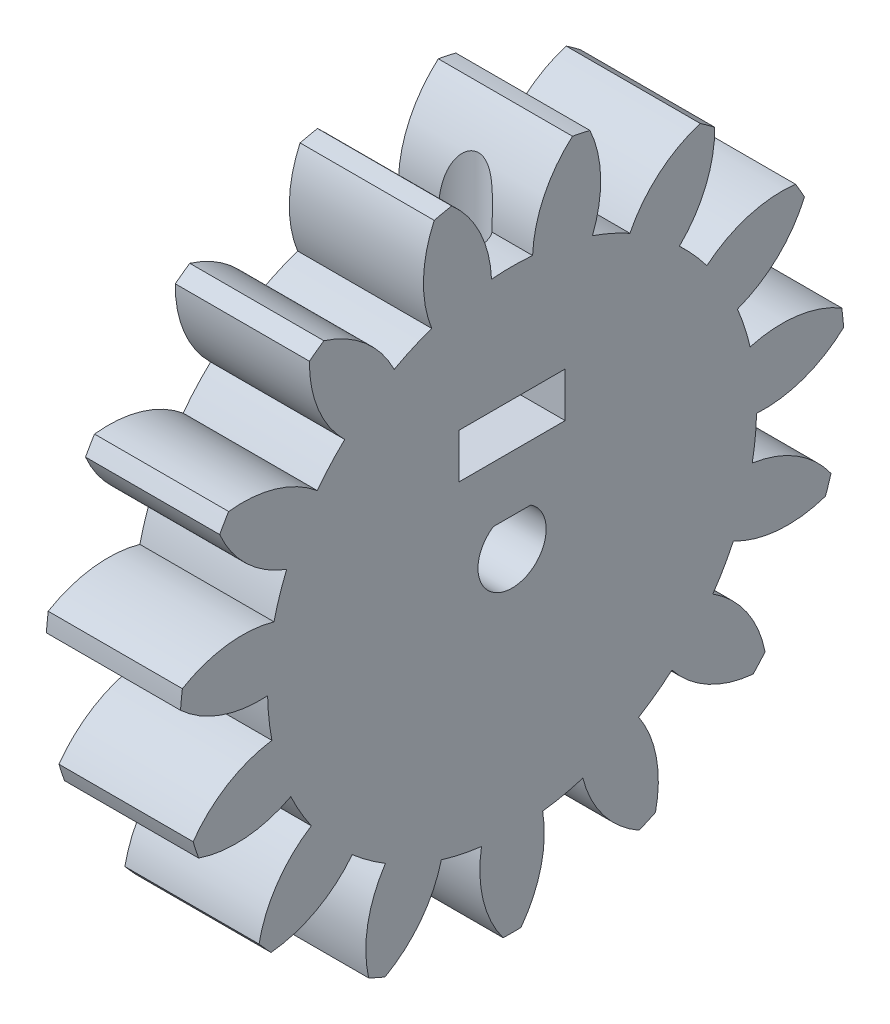
SolidWorks part; units mm, degrees
other "Markup1"
sketch "Sketch16" plane through (0, 29.2556, 29.6599) normal (0, 1, 0) x (0, 0, -1)
ref_plane "Plane1" through (0, 0, 0) normal (0, 0, 1) x (1, 0, 0)
ref_plane "Plane2" through (0, 0, 0) normal (0, 1, 0) x (1, 0, 0)
ref_plane "Plane3" through (0, 0, 0) normal (1, 0, 0) x (0, 0, -1)
sketch "HoldingSke" plane through (0, 0, 0) normal (0, 1, 0) x (1, 0, 0)
  line L0 (0, 0) -> (0.276, -0.0739)
  line L1 (-15, 0) -> (100, 0) construction
  line L2 (0, 0) -> (-2.1039, 2.3779)
  line L3 (0, 0) -> (-11.863, 4.5341)
  line L4 (0, 0) -> (8.3417, 2.2352)
  line L5 (0, 0) -> (-46.8476, -17.4728)
  line L6 (0, 0) -> (-8.2896, -5.593)
  line L7 (-2.1039, 2.3779) -> (8.6586, 51.2059)
  line L8 (-76.2, 54.61) -> (-75.2, 54.61)
  line L9 (-71.009, 38.7566) -> (-53.1078, 45.2721)
  line L10 (-76.2, 71.12) -> (104.1128, 71.12)
  line L11 (0, 0) -> (-10, 0)
  line L12 (-76.2, 101.6) -> (-76.083, 101.6)
  line L13 (24.9733, 27.94) -> (52.9518, 28.4284)
  line L14 (24.9733, 27.94) -> (24.9743, 27.94)
  line L15 (24.9733, 27.94) -> (100.4006, 29.5858)
  line L16 (-63.627, -3.5) -> (-12.827, -3.5)
  circle A0 centre (0, 0) radius 3
  circle A1 centre (0, 0) radius 21.874
  circle A2 centre (0, 0) radius 37.5
  circle A3 centre (0, 0) radius 3
  dimension "MHD" = 43.748
  dimension "Hub_dia" = 75
  dimension "Bore" = 6
  dimension "MBD" = 6
  dimension "Num_teeth" = 15
  dimension "Pitch" = 0.2857
  dimension "Overall_len" = 50
  dimension "Show_teeth" = 15
  dimension "Thickness" = 10
  dimension "OAL" = 50.0001
  dimension "T_dim" = 1
  dimension "Ap" = 20
  dimension "H" = 19.05
  dimension "Pitch_radius" = 180.3128
  dimension "Width" = 10
  dimension "Backlash" = 0.117
  dimension "Addendum_fac" = 1
  dimension "Dedendum_fac" = 1.25
  dimension "Clearance_fac" = 0.25
  dimension "Dedendum_add" = 0.001
  dimension "Module" = 3.5
sketch "BasProSke" plane through (0, 0, 0) normal (0, 1, 0) x (1, 0, 0)
  line L0 (-10, 0) -> (60, 0) construction
  line L1 (0, 0) -> (0, 29.75)
  line L2 (0, 0) -> (10, 0)
  line L3 (10, 0) -> (10, 29.75)
  line L4 (10, 29.75) -> (0, 29.75)
  dimension "Thickness" = 10
  dimension "Diameter" = 59.5
revolve "Base-Revolve" add sketch "BasProSke" angle 360 about L0
sketch "TooCutSke" plane through (0, 0, 0) normal (1, 0, 0) x (0, 0, -1)
  line L1 (0, 0) -> (0, 107) construction
  line L2 (0, 0) -> (-2.9485, 26.0839) construction
  line L3 (0, 0) -> (-10.8642, 51.1119) construction
  line L4 (-2.9485, 26.0839) -> (-5.4321, 25.556) construction
  arc A0 (1.8373, 21.7967) -> (-1.8373, 21.7967) centre (0, 0) ccw
  arc A1 (5.4253, 29.277) -> (-5.4253, 29.277) centre (0, 0) ccw
  circle A2 centre (0, 0) radius 26.25 construction
  circle A3 centre (0, 0) radius 24.6669 construction
  arc A4 (-1.8373, 21.7967) -> (-5.4253, 29.277) centre (-12.3284, 21.3651) ccw
  arc A5 (5.4253, 29.277) -> (1.8373, 21.7967) centre (12.3284, 21.3651) ccw
  dimension "Root_dia" = 43.748
  dimension "Overcut_dia" = 59.5508
  dimension "Pitch_dia" = 52.5
  dimension "Base_dia" = 49.3339
  dimension "Flank_rad" = 10.5
  dimension "Half_ang" = 12
  dimension "Half_CT" = 2.5391
extrude "ToothCut" cut sketch "TooCutSke" along normal through all
fillet "Breaks" [suppressed] radius 0.07 tangent propagation no
fillet "RootFillets" [suppressed] radius 0.876
pattern_circular "TeethCuts" count 15 every 24 about axis through (-10, 0, 0) along (1, 0, 0) of "ToothCut", "RootFillets", "Breaks"
sketch "HubNeaOneSke" plane through (0, 0, 0) normal (-1, 0, 0) x (0, 0, 1)
  circle A0 centre (0, 0) radius 21.874
  dimension "Diameter" = 43.748
extrude "HubNearOne" [suppressed] add sketch "HubNeaOneSke" along normal blind 40.0001
sketch "HubNeaBotSke" plane through (0, 0, 0) normal (-1, 0, 0) x (0, 0, 1)
  circle A0 centre (0, 0) radius 21.874
  dimension "Diameter" = 43.748
extrude "HubNearBoth" [suppressed] add sketch "HubNeaBotSke" along normal blind 20
ref_plane "FarPln" through (10, 0, 0) normal (1, 0, 0) x (0, 0, -1)
sketch "HubFarSke" plane through (10, 0, 0) normal (1, 0, 0) x (0, 0, -1)
  circle A0 centre (0, 0) radius 21.874
  dimension "Diameter" = 43.748
extrude "HubFar" [suppressed] add sketch "HubFarSke" along normal blind 20
sketch "BorSke" plane through (0, 0, 0) normal (1, 0, 0) x (0, 0, -1)
  circle A0 centre (0, 0) radius 3
  dimension "Diameter" = 6
extrude "Bore" cut sketch "BorSke" along normal mid plane 100.0001
sketch "KeySke" plane through (0, 0, 0) normal (1, 0, 0) x (0, 0, -1)
  line L0 (-1, 0) -> (-1, 4)
  line L1 (-1, 4) -> (1, 4)
  line L2 (1, 4) -> (1, 0)
  line L3 (0, 0) -> (0, 34) construction
  line L4 (-1, 0) -> (1, 0)
  dimension "Offset" = 4
  dimension "Width" = 2
extrude "Keyway" [suppressed] cut sketch "KeySke" along normal mid plane 100.0001
pattern_circular "Keyway2" [suppressed] count 2 every 90 about axis through (-10, 0, 0) along (1, 0, 0) reverse direction yes
sketch "Sketch1" plane through (0, 0, 0) normal (-1, 0, 0) x (0, 0, 1)
  circle A0 centre (0, 0) radius 3.05
  dimension "D1" = 6.1
extrude "Cut-Extrude1" cut sketch "Sketch1" against normal blind 10
sketch "Sketch2" plane through (0, 0, 0) normal (-1, 0, 0) x (0, 0, 1)
  circle A0 centre (0, 0) radius 4.0254
extrude "Boss-Extrude1" add sketch "Sketch2" against normal blind 4
sketch "Sketch5" plane through (10, 0, 0) normal (1, 0, 0) x (0, 0, -1)
  line L5 (5.1432, 3.05) -> (-4.9527, 3.05)
  line L6 (5.1432, 3.05) -> (5.1432, 2.55)
  line L7 (5.1432, 2.55) -> (-4.9527, 2.55)
  line L8 (-4.9527, 3.05) -> (-4.9527, 2.55)
  dimension "D1" = 0.5
extrude "Boss-Extrude5" add sketch "Sketch5" against normal blind 6
sketch "Sketch6" plane through (0, 0, 0) normal (-1, 0, 0) x (0, 0, 1)
  line L5 (-0.625, -1.625) -> (0.625, -1.625)
  line L6 (-0.625, -1.625) -> (-0.625, 1.625)
  line L7 (-0.625, 1.625) -> (0.625, 1.625)
  line L8 (0.625, -1.625) -> (0.625, 1.625)
  dimension "D2" = 1.25
  dimension "D3" = 3.25
extrude "Cut-Extrude2" cut sketch "Sketch6" against normal blind 3.25
sketch "Sketch7" plane through (0, 0, 0) normal (0, 1, 0) x (1, 0, 0)
  line L0 (10, -1.8373) -> (10, 1.8373) construction
  circle A0 centre (6, 0) radius 1.5
  dimension "D1" = 3
  dimension "D2" = 4
extrude "Cut-Extrude3" cut sketch "Sketch7" against normal blind 30 from offset 30
sketch "Sketch8" plane through (0, 0, 0) normal (0, 1, 0) x (1, 0, 0)
  circle A0 centre (6, 0) radius 3
  dimension "D1" = 6
extrude "Cut-Extrude4" cut sketch "Sketch8" against normal blind 14 from offset 30
sketch "Sketch11" plane through (10, 0, 0) normal (1, 0, 0) x (0, 0, -1)
  arc A60 (-29.6599, 2.3133) -> (-21.8693, -0.4512) centre (-22.5367, 10.0276) ccw
  arc A61 (-21.8693, -0.4512) -> (-21.4853, -4.1056) centre (0, 0) ccw
  arc A62 (-21.4853, -4.1056) -> (-28.5308, -8.4294) centre (-19.9594, -14.4941) ccw
  arc A63 (-28.5308, -8.4294) -> (-28.0366, -9.9505) centre (0, 0) ccw
  arc A64 (-28.0366, -9.9505) -> (-19.7951, -9.3072) centre (-24.6669, -0.0059) ccw
  arc A65 (-19.7951, -9.3072) -> (-17.9579, -12.4895) centre (0, 0) ccw
  arc A66 (-17.9579, -12.4895) -> (-22.6357, -19.3052) centre (-12.3385, -21.3593) ccw
  arc A67 (-22.6357, -19.3052) -> (-21.5655, -20.4937) centre (0, 0) ccw
  arc A68 (-21.5655, -20.4937) -> (-14.2982, -16.554) centre (-22.532, -10.0383) ccw
  arc A69 (-14.2982, -16.554) -> (-11.3254, -18.7138) centre (0, 0) ccw
  arc A70 (-11.3254, -18.7138) -> (-12.8266, -26.8429) centre (-2.5842, -24.5312) ccw
  arc A71 (-12.8266, -26.8429) -> (-11.3655, -27.4934) centre (0, 0) ccw
  arc A72 (-11.3655, -27.4934) -> (-6.3289, -20.9384) centre (-16.501, -18.335) ccw
  arc A73 (-6.3289, -20.9384) -> (-2.7347, -21.7024) centre (0, 0) ccw
  arc A74 (-2.7347, -21.7024) -> (-0.7997, -29.7393) centre (7.6169, -23.4615) ccw
  arc A75 (-0.7997, -29.7393) -> (0.7997, -29.7393) centre (0, 0) ccw
  arc A76 (0.7997, -29.7393) -> (2.7347, -21.7024) centre (-7.6169, -23.4615) ccw
  arc A77 (2.7347, -21.7024) -> (6.3289, -20.9384) centre (0, 0) ccw
  arc A78 (6.3289, -20.9384) -> (11.3655, -27.4934) centre (16.501, -18.335) ccw
  arc A79 (11.3655, -27.4934) -> (12.8266, -26.8429) centre (0, 0) ccw
  arc A80 (12.8266, -26.8429) -> (11.3254, -18.7138) centre (2.5842, -24.5312) ccw
  arc A81 (11.3254, -18.7138) -> (14.2982, -16.554) centre (0, 0) ccw
  arc A82 (14.2982, -16.554) -> (21.5655, -20.4937) centre (22.532, -10.0383) ccw
  arc A83 (21.5655, -20.4937) -> (22.6357, -19.3052) centre (0, 0) ccw
  arc A84 (22.6357, -19.3052) -> (17.9579, -12.4895) centre (12.3385, -21.3593) ccw
  arc A85 (17.9579, -12.4895) -> (19.7951, -9.3072) centre (0, 0) ccw
  arc A86 (19.7951, -9.3072) -> (28.0366, -9.9505) centre (24.6669, -0.0059) ccw
  arc A87 (28.0366, -9.9505) -> (28.5308, -8.4294) centre (0, 0) ccw
  arc A88 (28.5308, -8.4294) -> (21.4853, -4.1056) centre (19.9594, -14.4941) ccw
  arc A89 (21.4853, -4.1056) -> (21.8693, -0.4512) centre (0, 0) ccw
  arc A90 (21.8693, -0.4512) -> (29.6599, 2.3133) centre (22.5367, 10.0276) ccw
  arc A91 (29.6599, 2.3133) -> (29.4927, 3.9039) centre (0, 0) ccw
  arc A92 (29.4927, 3.9039) -> (21.2976, 4.9882) centre (24.1291, -5.1228) ccw
  arc A93 (21.2976, 4.9882) -> (20.1622, 8.4829) centre (0, 0) ccw
  arc A94 (20.1622, 8.4829) -> (26.1548, 14.1771) centre (16.5098, 18.3272) ccw
  arc A95 (26.1548, 14.1771) -> (25.3551, 15.5622) centre (0, 0) ccw
  arc A96 (25.3551, 15.5622) -> (17.4275, 13.2195) centre (24.1267, 5.1343) ccw
  arc A97 (17.4275, 13.2195) -> (14.9687, 15.9502) centre (0, 0) ccw
  arc A98 (14.9687, 15.9502) -> (18.1272, 23.5895) centre (7.6281, 23.4578) ccw
  arc A99 (18.1272, 23.5895) -> (16.8333, 24.5296) centre (0, 0) ccw
  arc A100 (16.8333, 24.5296) -> (10.5439, 19.165) centre (19.9525, 14.5036) ccw
  arc A101 (10.5439, 19.165) -> (7.1871, 20.6596) centre (0, 0) ccw
  arc A102 (7.1871, 20.6596) -> (6.9653, 28.9231) centre (-2.5726, 24.5324) ccw
  arc A103 (6.9653, 28.9231) -> (5.4009, 29.2556) centre (0, 0) ccw
  arc A104 (5.4009, 29.2556) -> (1.8373, 21.7967) centre (12.3284, 21.3651) ccw
  arc A105 (1.8373, 21.7967) -> (-1.8373, 21.7967) centre (0, 0) ccw
  arc A106 (-1.8373, 21.7967) -> (-5.4009, 29.2556) centre (-12.3284, 21.3651) ccw
  arc A107 (-5.4009, 29.2556) -> (-6.9653, 28.9231) centre (0, 0) ccw
  arc A108 (-6.9653, 28.9231) -> (-7.1871, 20.6596) centre (2.5726, 24.5324) ccw
  arc A109 (-7.1871, 20.6596) -> (-10.5439, 19.165) centre (0, 0) ccw
  arc A110 (-10.5439, 19.165) -> (-16.8333, 24.5296) centre (-19.9525, 14.5036) ccw
  arc A111 (-16.8333, 24.5296) -> (-18.1272, 23.5895) centre (0, 0) ccw
  arc A112 (-18.1272, 23.5895) -> (-14.9687, 15.9502) centre (-7.6281, 23.4578) ccw
  arc A113 (-14.9687, 15.9502) -> (-17.4275, 13.2195) centre (0, 0) ccw
  arc A114 (-17.4275, 13.2195) -> (-25.3551, 15.5622) centre (-24.1267, 5.1343) ccw
  arc A115 (-25.3551, 15.5622) -> (-26.1548, 14.1771) centre (0, 0) ccw
  arc A116 (-26.1548, 14.1771) -> (-20.1622, 8.4829) centre (-16.5098, 18.3272) ccw
  arc A117 (-20.1622, 8.4829) -> (-21.2976, 4.9882) centre (0, 0) ccw
  arc A118 (-21.2976, 4.9882) -> (-29.4927, 3.9039) centre (-24.1291, -5.1228) ccw
  arc A119 (-29.4927, 3.9039) -> (-29.6599, 2.3133) centre (0, 0) ccw
  arc A120 (-29.6599, 2.3133) -> (-21.8693, -0.4512) centre (-22.5367, 10.0276) ccw
  arc A121 (-21.8693, -0.4512) -> (-21.4853, -4.1056) centre (0, 0) ccw
  arc A122 (-21.4853, -4.1056) -> (-28.5308, -8.4294) centre (-19.9594, -14.4941) ccw
  arc A123 (-28.5308, -8.4294) -> (-28.0366, -9.9505) centre (0, 0) ccw
  arc A124 (-28.0366, -9.9505) -> (-19.7951, -9.3072) centre (-24.6669, -0.0059) ccw
  arc A125 (-19.7951, -9.3072) -> (-17.9579, -12.4895) centre (0, 0) ccw
  arc A126 (-17.9579, -12.4895) -> (-22.6357, -19.3052) centre (-12.3385, -21.3593) ccw
  arc A127 (-22.6357, -19.3052) -> (-21.5655, -20.4937) centre (0, 0) ccw
  arc A128 (-21.5655, -20.4937) -> (-14.2982, -16.554) centre (-22.532, -10.0383) ccw
  arc A129 (-14.2982, -16.554) -> (-11.3254, -18.7138) centre (0, 0) ccw
  arc A130 (-11.3254, -18.7138) -> (-12.8266, -26.8429) centre (-2.5842, -24.5312) ccw
  arc A131 (-12.8266, -26.8429) -> (-11.3655, -27.4934) centre (0, 0) ccw
  arc A132 (-11.3655, -27.4934) -> (-6.3289, -20.9384) centre (-16.501, -18.335) ccw
  arc A133 (-6.3289, -20.9384) -> (-2.7347, -21.7024) centre (0, 0) ccw
  arc A134 (-2.7347, -21.7024) -> (-0.7997, -29.7393) centre (7.6169, -23.4615) ccw
  arc A135 (-0.7997, -29.7393) -> (0.7997, -29.7393) centre (0, 0) ccw
  arc A136 (0.7997, -29.7393) -> (2.7347, -21.7024) centre (-7.6169, -23.4615) ccw
  arc A137 (2.7347, -21.7024) -> (6.3289, -20.9384) centre (0, 0) ccw
  arc A138 (6.3289, -20.9384) -> (11.3655, -27.4934) centre (16.501, -18.335) ccw
  arc A139 (11.3655, -27.4934) -> (12.8266, -26.8429) centre (0, 0) ccw
  arc A140 (12.8266, -26.8429) -> (11.3254, -18.7138) centre (2.5842, -24.5312) ccw
  arc A141 (11.3254, -18.7138) -> (14.2982, -16.554) centre (0, 0) ccw
  arc A142 (14.2982, -16.554) -> (21.5655, -20.4937) centre (22.532, -10.0383) ccw
  arc A143 (21.5655, -20.4937) -> (22.6357, -19.3052) centre (0, 0) ccw
  arc A144 (22.6357, -19.3052) -> (17.9579, -12.4895) centre (12.3385, -21.3593) ccw
  arc A145 (17.9579, -12.4895) -> (19.7951, -9.3072) centre (0, 0) ccw
  arc A146 (19.7951, -9.3072) -> (28.0366, -9.9505) centre (24.6669, -0.0059) ccw
  arc A147 (28.0366, -9.9505) -> (28.5308, -8.4294) centre (0, 0) ccw
  arc A148 (28.5308, -8.4294) -> (21.4853, -4.1056) centre (19.9594, -14.4941) ccw
  arc A149 (21.4853, -4.1056) -> (21.8693, -0.4512) centre (0, 0) ccw
  arc A150 (21.8693, -0.4512) -> (29.6599, 2.3133) centre (22.5367, 10.0276) ccw
  arc A151 (29.6599, 2.3133) -> (29.4927, 3.9039) centre (0, 0) ccw
  arc A152 (29.4927, 3.9039) -> (21.2976, 4.9882) centre (24.1291, -5.1228) ccw
  arc A153 (21.2976, 4.9882) -> (20.1622, 8.4829) centre (0, 0) ccw
  arc A154 (20.1622, 8.4829) -> (26.1548, 14.1771) centre (16.5098, 18.3272) ccw
  arc A155 (26.1548, 14.1771) -> (25.3551, 15.5622) centre (0, 0) ccw
  arc A156 (25.3551, 15.5622) -> (17.4275, 13.2195) centre (24.1267, 5.1343) ccw
  arc A157 (17.4275, 13.2195) -> (14.9687, 15.9502) centre (0, 0) ccw
  arc A158 (14.9687, 15.9502) -> (18.1272, 23.5895) centre (7.6281, 23.4578) ccw
  arc A159 (18.1272, 23.5895) -> (16.8333, 24.5296) centre (0, 0) ccw
  arc A160 (16.8333, 24.5296) -> (10.5439, 19.165) centre (19.9525, 14.5036) ccw
  arc A161 (10.5439, 19.165) -> (7.1871, 20.6596) centre (0, 0) ccw
  arc A162 (7.1871, 20.6596) -> (6.9653, 28.9231) centre (-2.5726, 24.5324) ccw
  arc A163 (6.9653, 28.9231) -> (5.4009, 29.2556) centre (0, 0) ccw
  arc A164 (5.4009, 29.2556) -> (1.8373, 21.7967) centre (12.3284, 21.3651) ccw
  arc A165 (1.8373, 21.7967) -> (-1.8373, 21.7967) centre (0, 0) ccw
  arc A166 (-1.8373, 21.7967) -> (-5.4009, 29.2556) centre (-12.3284, 21.3651) ccw
  arc A167 (-5.4009, 29.2556) -> (-6.9653, 28.9231) centre (0, 0) ccw
  arc A168 (-6.9653, 28.9231) -> (-7.1871, 20.6596) centre (2.5726, 24.5324) ccw
  arc A169 (-7.1871, 20.6596) -> (-10.5439, 19.165) centre (0, 0) ccw
  arc A170 (-10.5439, 19.165) -> (-16.8333, 24.5296) centre (-19.9525, 14.5036) ccw
  arc A171 (-16.8333, 24.5296) -> (-18.1272, 23.5895) centre (0, 0) ccw
  arc A172 (-18.1272, 23.5895) -> (-14.9687, 15.9502) centre (-7.6281, 23.4578) ccw
  arc A173 (-14.9687, 15.9502) -> (-17.4275, 13.2195) centre (0, 0) ccw
  arc A174 (-17.4275, 13.2195) -> (-25.3551, 15.5622) centre (-24.1267, 5.1343) ccw
  arc A175 (-25.3551, 15.5622) -> (-26.1548, 14.1771) centre (0, 0) ccw
  arc A176 (-26.1548, 14.1771) -> (-20.1622, 8.4829) centre (-16.5098, 18.3272) ccw
  arc A177 (-20.1622, 8.4829) -> (-21.2976, 4.9882) centre (0, 0) ccw
  arc A178 (-21.2976, 4.9882) -> (-29.4927, 3.9039) centre (-24.1291, -5.1228) ccw
  arc A179 (-29.4927, 3.9039) -> (-29.6599, 2.3133) centre (0, 0) ccw
  dimension "D1" = 0
extrude "Boss-Extrude7" add sketch "Sketch11" along normal blind 2
sketch "Sketch12" plane through (12, 0, 0) normal (1, 0, 0) x (0, 0, -1)
  circle A0 centre (0, 0) radius 3.05
  dimension "D1" = 6.1
extrude "Cut-Extrude5" cut sketch "Sketch12" against normal blind 2
extrude "Boss-Extrude8" add sketch "Sketch5<2>" along normal blind 2
sketch "Sketch5<2>" plane through (10, 0, 0) normal (1, 0, 0) x (0, 0, -1) same geometry as "Sketch5"
sketch "Sketch15" plane through (0, 16, 0) normal (0, 1, 0) x (1, 0, 0)
  circle A0 centre (6, 0) radius 1.75
  dimension "D1" = 3.5
extrude "Cut-Extrude6" cut sketch "Sketch15" against normal blind 16
sketch "Sketch18" plane through (12, 0, 0) normal (1, 0, 0) x (0, 0, -1)
  line L0 (1.6733, 2.55) -> (-1.6733, 2.55) construction
  line L1 (-4.75, 7.55) -> (4.75, 7.55)
  line L2 (-4.75, 7.55) -> (-4.75, 11.55)
  line L3 (-4.75, 11.55) -> (4.75, 11.55)
  line L4 (4.75, 7.55) -> (4.75, 11.55)
  line L5 (-4.75, 7.55) -> (4.75, 11.55) construction
  line L6 (-4.75, 11.55) -> (4.75, 7.55) construction
  line L7 (0, 2.55) -> (0, 7.55)
  point P0 (0, 9.55)
  dimension "D1" = 4
  dimension "D2" = 9.5
  dimension "D3" = 5
  dimension "D4" = 90
extrude "Cut-Extrude7" cut sketch "Sketch18" against normal through all contours L1 L4 L3 L2 region at (12, 9.55, 0)
sketch "Sketch20" plane through (0, 16, 0) normal (0, 1, 0) x (1, 0, 0)
  circle A1 centre (6, 0) radius 3
  circle A2 centre (6, 0) radius 3
  dimension "D1" = 0
extrude "Cut-Extrude9" cut sketch "Sketch20" against normal up to surface (4.45 mm away) contours A2 up to face at (6, 11.55, 0)
equation "' \"Module@HoldingSke\" = 6.35"
equation "' \"Num_teeth@HoldingSke\" = 12"
equation "' \"Ap@HoldingSke\" =  20"
equation "' \"Ap@HoldingSke\" = 20"
equation "' \"Width@HoldingSke\" = 0.5 * 25.4"
equation "' \"Hub_dia@HoldingSke\"= 1 * 25.4"
equation "' \"Hub_dia@HoldingSke\" = 1 * 25.4"
equation "' \"Overall_len@HoldingSke\" = 1.0 * 25.4"
equation "' \"Bore@HoldingSke\" = 0.75 * 25.4"
equation "' \"T_dim@HoldingSke\" = 0.1 * 25.4"
equation "' \"Width@KeySke\" = 0.25 * 25.4"
equation "' \"Show_teeth@HoldingSke\" = 13"
equation "' \"Backlash@HoldingSke\" = 0.009 * 25.4"
equation "' \"Addendum_fac@HoldingSke\" = 1.0"
equation "' \"Dedendum_fac@HoldingSke\" = 1.25"
equation "' \"Dedendum_add@HoldingSke\" = 0.00005 * 25.4"
equation "' \"Clearance_fac@HoldingSke\" = 0.25"
equation "\"Pitch@HoldingSke\" = 1 / \"Module@HoldingSke\""
equation "\"Overcut_dia@TooCutSke\" = (\"Num_teeth@HoldingSke\" + 2 * \"Addendum_fac@HoldingSke\") / \"Pitch@HoldingSke\" + 0.002 * 25.4"
equation "\"Pitch_dia@TooCutSke\" = \"Num_teeth@HoldingSke\" / \"Pitch@HoldingSke\""
equation "\"Base_dia@TooCutSke\" = \"Num_teeth@HoldingSke\" / \"Pitch@HoldingSke\" * cos((\"Ap@HoldingSke\"  * 3.14159265 / 180))"
equation "\"Root_dia@TooCutSke\" = (\"Num_teeth@HoldingSke\" + 2) / \"Pitch@HoldingSke\" - 2 * (\"Addendum_fac@HoldingSke\" + \"Dedendum_fac@HoldingSke\") / \"Pitch@HoldingSke\" - \"Dedendum_add@HoldingSke\" * 2"
equation "\"Half_ang@TooCutSke\" = 180 / \"Num_teeth@HoldingSke\""
equation "\"Half_CT@TooCutSke\" = \"Num_teeth@HoldingSke\" / \"Pitch@HoldingSke\" * sin((3.14159265 / 2 / \"Num_teeth@HoldingSke\")) / 2 - 7 * \"Backlash@HoldingSke\" / 4"
equation "\"Flank_rad@TooCutSke\" = \"Num_teeth@HoldingSke\" / \"Pitch@HoldingSke\" / 5"
equation "\"Radius@RootFillets\" = \"Clearance_fac@HoldingSke\" / \"Pitch@HoldingSke\" + \"Dedendum_add@HoldingSke\""
equation "\"Break_rad@Breaks\" = 0.02 / \"Pitch@HoldingSke\""
equation "\"Thickness@HoldingSke\" = \"Width@HoldingSke\""
equation "\"OAL@HoldingSke\" = \"Thickness@HoldingSke\""
equation "\"MHD@HoldingSke\" = (\"Num_teeth@HoldingSke\" + 2) / \"Pitch@HoldingSke\" - 2 * (\"Addendum_fac@HoldingSke\" + \"Dedendum_fac@HoldingSke\")  / \"Pitch@HoldingSke\" - \"Dedendum_add@HoldingSke\" * 2"
equation "\"MBD@HoldingSke\" = (\"Num_teeth@HoldingSke\" + 2) / \"Pitch@HoldingSke\" - 2 * (\"Addendum_fac@HoldingSke\" + \"Dedendum_fac@HoldingSke\")  / \"Pitch@HoldingSke\" - \"Dedendum_add@HoldingSke\" * 2 - 0.002 * 25.4"
equation "\"MHD@HoldingSke\" = ((sgn( \"MHD@HoldingSke\" - \"Hub_dia@HoldingSke\" )-1)*( \"MHD@HoldingSke\" - \"Hub_dia@HoldingSke\" ))/-2+ \"Hub_dia@HoldingSke\""
equation "\"MBD@HoldingSke\" = ((sgn( \"MBD@HoldingSke\" - \"Bore@HoldingSke\" )-1)*( \"MBD@HoldingSke\" - \"Bore@HoldingSke\" ))/-2+ \"Bore@HoldingSke\""
equation "\"OAL@HoldingSke\" = ((sgn( \"OAL@HoldingSke\" - \"Overall_len@HoldingSke\" )+1)*( \"OAL@HoldingSke\" - \"Overall_len@HoldingSke\" ))/2 + \"Overall_len@HoldingSke\" + 0.000002 * 25.4"
equation "\"Num_teeth@TeethCuts\" = int( \"Show_teeth@HoldingSke\" ) + 1"
equation "\"Num_teeth@TeethCuts\" = ((sgn( \"Num_teeth@TeethCuts\" - \"Num_teeth@HoldingSke\" )-1)*( \"Num_teeth@TeethCuts\" - \"Num_teeth@HoldingSke\" ))/-2+ \"Num_teeth@HoldingSke\""
equation "\"Num_teeth@TeethCuts\" = ((sgn( \"Num_teeth@TeethCuts\" - 2.0)+1)*( \"Num_teeth@TeethCuts\" - 2.0))/2 +2.0"
equation "\"Angle@TeethCuts\" = 360.0 / \"Num_teeth@HoldingSke\""
equation "\"Diameter@BasProSke\" = (\"Num_teeth@HoldingSke\" + 2 * \"Addendum_fac@HoldingSke\") / \"Pitch@HoldingSke\""
equation "\"Thickness@BasProSke\"  = \"Thickness@HoldingSke\""
equation "' \"Fillet_rad@BasProSke\" =  \"Thickness@HoldingSke\" * 0.05"
equation "' \"Fillet_rad@BasProSke\" = \"Thickness@HoldingSke\" * 0.05"
equation "\"MHD@HoldingSke\" = ((sgn( \"MHD@HoldingSke\" - \"Root_dia@TooCutSke\" )-1)*( \"MHD@HoldingSke\" - \"Root_dia@TooCutSke\" ))/-2+ \"Root_dia@TooCutSke\""
equation "\"Diameter@HubNeaOneSke\" = \"MHD@HoldingSke\""
equation "\"Length@HubNearOne\" = \"OAL@HoldingSke\" - \"Thickness@BasProSke\""
equation "\"Diameter@HubNeaBotSke\" = \"MHD@HoldingSke\""
equation "\"Length@HubNearBoth\" = ( \"OAL@HoldingSke\" - \"Thickness@BasProSke\" ) / 2.0"
equation "\"Thickness@FarPln\" = \"Thickness@BasProSke\""
equation "\"Diameter@HubFarSke\" = \"MHD@HoldingSke\""
equation "\"Length@HubFar\" = ( \"OAL@HoldingSke\" - \"Thickness@BasProSke\" ) / 2.0"
equation "\"Diameter@BorSke\" = \"MBD@HoldingSke\""
equation "\"D1@Bore\" = \"OAL@HoldingSke\" * 2.0"
equation "\"D1@Keyway\" = \"OAL@HoldingSke\" * 2.0"
equation "\"Offset@KeySke\" = \"T_dim@HoldingSke\" + \"MBD@HoldingSke\" / 2.0"
